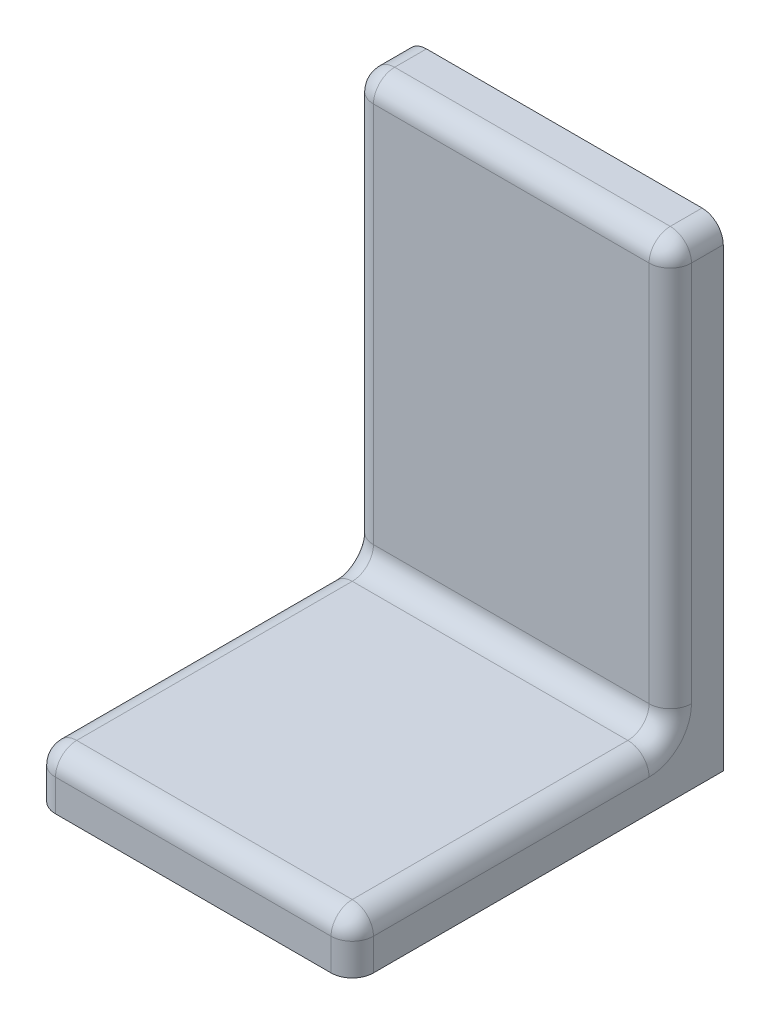
SolidWorks part; units mm, degrees
ref_plane "Front Plane" through (0, 0, 0) normal (0, 0, 1) x (1, 0, 0)
ref_plane "Top Plane" through (0, 0, 0) normal (0, 1, 0) x (1, 0, 0)
ref_plane "Right Plane" through (0, 0, 0) normal (1, 0, 0) x (0, 0, -1)
sketch "Sketch1" plane through (0, 0, 0) normal (0, 1, 0) x (1, 0, 0)
  line L1 (-300, -300) -> (300, -300)
  line L2 (-300, -300) -> (-300, 300)
  line L3 (-300, 300) -> (300, 300)
  line L4 (300, -300) -> (300, 300)
  line L5 (-300, -300) -> (300, 300) construction
  line L6 (-300, 300) -> (300, -300) construction
  point P0 (0, 0)
  dimension "D1" = 600
  dimension "D2" = 600
extrude "Boss-Extrude1" add sketch "Sketch1" along normal blind 100
sketch "Sketch2" plane through (0, 0, -300) normal (0, 0, -1) x (-1, 0, 0)
  line L1 (300, 0) -> (-300, 0)
  line L2 (300, 0) -> (300, 900)
  line L3 (300, 900) -> (-300, 900)
  line L4 (-300, 0) -> (-300, 900)
  dimension "D1" = 900
extrude "Boss-Extrude2" add sketch "Sketch2" along normal blind 100
fillet "Fillet1" radius 40 11 edges at (-300, 900, -350) (300, 900, -350) (-300, 50, 300) (-300, 100, 0) (0, 100, 300) (300, 50, 300) (300, 100, 0) (300, 500, -300) (0, 900, -300) (-300, 500, -300) (0, 100, -300)
